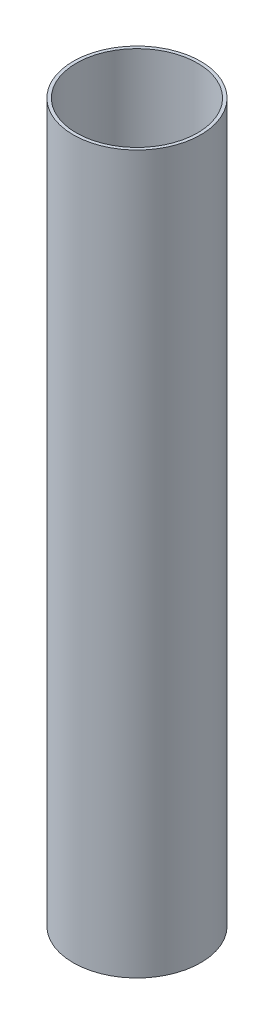
SolidWorks part; units mm, degrees
ref_plane "Front Plane" through (0, 0, 0) normal (0, 0, 1) x (1, 0, 0)
ref_plane "Top Plane" through (0, 0, 0) normal (0, 1, 0) x (1, 0, 0)
ref_plane "Right Plane" through (0, 0, 0) normal (1, 0, 0) x (0, 0, -1)
sketch "Sketch1" plane through (0, 0, 0) normal (0, 1, 0) x (1, 0, 0)
  circle A0 centre (0, 0) radius 38
  circle A1 centre (0, 0) radius 40
  dimension "D1" = 80
  dimension "D2" = 2
extrude "Boss-Extrude1" add sketch "Sketch1" along normal blind 450
